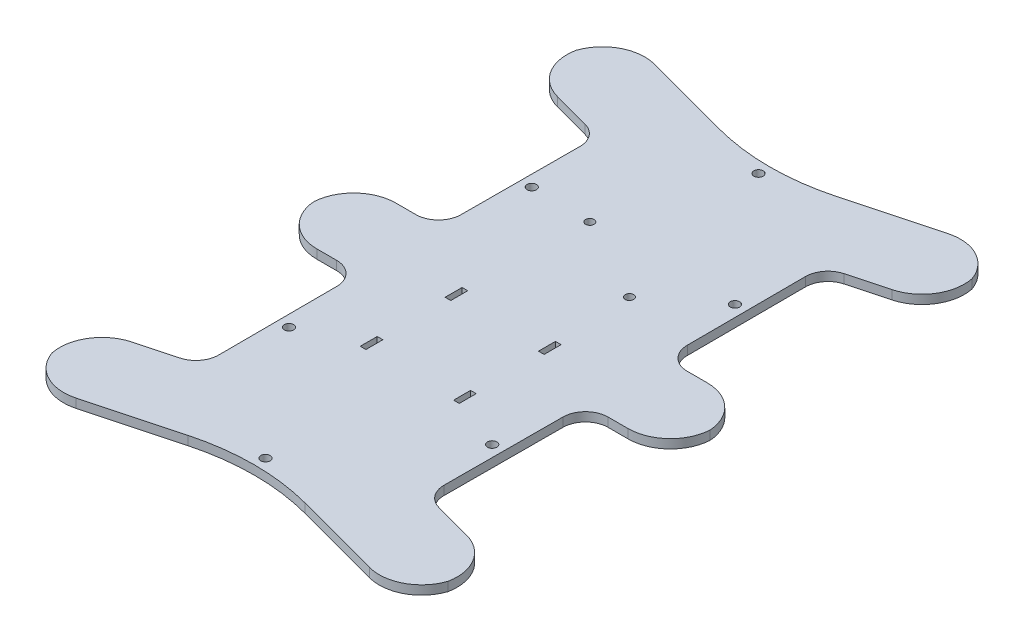
SolidWorks part; units mm, degrees
ref_plane "Front Plane" through (0, 0, 0) normal (0, 0, 1) x (1, 0, 0)
ref_plane "Top Plane" through (0, 0, 0) normal (0, 1, 0) x (1, 0, 0)
ref_plane "Right Plane" through (0, 0, 0) normal (1, 0, 0) x (0, 0, -1)
sketch "Sketch1" plane through (0, 0, 0) normal (0, 1, 0) x (1, 0, 0)
  line L0 (0, 32.1883) -> (0, -21.4181) construction
  line L1 (0, 0) -> (27.1703, 0) construction
  line L2 (-70, 14) -> (-40, 14)
  line L3 (-40, 14) -> (-39.8161, 70)
  line L4 (-39.8161, 70) -> (-73.6235, 79.0587)
  line L5 (-66.3765, 106.1046) -> (0, 88.3191)
  line L10 (-66.3765, 106.1046) -> (-73.6235, 79.0587) construction
  line L12 (-70, 14) -> (-70, -14) construction
  line L14 (-66.3765, -106.1046) -> (0, -88.3191)
  line L15 (-39.8161, -70) -> (-73.6235, -79.0587)
  line L16 (-40, -14) -> (-39.8161, -70)
  line L17 (-70, -14) -> (-40, -14)
  line L18 (66.3765, -106.1046) -> (0, -88.3191)
  line L19 (66.3765, 106.1046) -> (0, 88.3191)
  line L20 (70, 14) -> (70, -14) construction
  line L21 (66.3765, 106.1046) -> (73.6235, 79.0587) construction
  line L22 (70, -14) -> (40, -14)
  line L23 (40, -14) -> (39.8161, -70)
  line L24 (39.8161, -70) -> (73.6235, -79.0587)
  line L25 (39.8161, 70) -> (73.6235, 79.0587)
  line L26 (40, 14) -> (39.8161, 70)
  line L27 (70, 14) -> (40, 14)
  arc A0 (-70, 14) -> (-70, -14) centre (-70, 0) ccw
  arc A1 (-66.3765, 106.1046) -> (-73.6235, 79.0587) centre (-70, 92.5816) ccw
  arc A11 (-66.3765, -106.1046) -> (-73.6235, -79.0587) centre (-70, -92.5816) cw
  arc A18 (66.3765, -106.1046) -> (73.6235, -79.0587) centre (70, -92.5816) ccw
  arc A22 (66.3765, 106.1046) -> (73.6235, 79.0587) centre (70, 92.5816) cw
  arc A23 (70, 14) -> (70, -14) centre (70, 0) cw
  point P118 (-83.523, 96.2051)
  dimension "D2" = 14
  dimension "D3" = 70
  dimension "D1" = 75
  dimension "D5" = 30
  dimension "D6" = 35
  dimension "D7" = 56
extrude "Boss-Extrude1" add sketch "Sketch1" along normal blind 3.175
fillet "Fillet1" radius 80 2 edges at (0, 1.5875, -88.3191) (0, 1.5875, 88.3191)
fillet "Fillet2" radius 8 8 edges at (39.8161, 1.5875, 70) (40, 1.5875, 14) (40, 1.5875, -14) (39.8161, 1.5875, -70) (-39.8161, 1.5875, -70) (-40, 1.5875, -14) (-40, 1.5875, 14) (-39.8161, 1.5875, 70)
sketch "Sketch2" plane through (0, 3.175, 0) normal (0, 1, 0) x (1, 0, 0)
  line L0 (0, 91.1411) -> (0, -91.1411) construction
  line L1 (-84, 0) -> (84, 0) construction
  line L2 (39.9738, 21.9737) -> (39.8363, 63.8405) construction
  line L3 (-39.8363, 63.8405) -> (-39.9738, 21.9737) construction
  line L4 (-39.9051, 42.9071) -> (39.9051, 42.9071) construction
  arc A0 (-20.7055, 93.8671) -> (20.7055, 93.8671) centre (0, 171.1411) ccw construction
  arc A1 (20.7055, -93.8671) -> (-20.7055, -93.8671) centre (0, -171.1411) ccw construction
  arc A2 (-70, 14) -> (-70, -14) centre (-70, 0) ccw construction
  arc A3 (70, -14) -> (70, 14) centre (70, 0) ccw construction
  circle A4 centre (0, 87.1411) radius 1.65
  circle A5 centre (-35.905, 42.9071) radius 1.65
  circle A6 centre (35.905, 42.9071) radius 1.65
  circle A7 centre (35.905, -42.9071) radius 1.65
  circle A8 centre (0, -87.1411) radius 1.65
  circle A9 centre (-35.905, -42.9071) radius 1.65
  point P18 (39.9051, 42.9071)
  point P21 (-39.9051, 42.9071)
  dimension "D4" = 3.3
  dimension "D1" = 4
  dimension "D2" = 4
  dimension "D3" = 4
extrude "Cut-Extrude1" cut sketch "Sketch2" against normal blind 10
sketch "Sketch3" plane through (0, 3.175, 0) normal (0, 1, 0) x (1, 0, 0)
  arc A0 (13.5, 26.5) -> (16.5, 26.5) centre (15, 26.5) ccw construction
  arc A1 (16.5, 26.5) -> (13.5, 26.5) centre (15, 26.5) ccw construction
  arc A2 (-16.5, 42.5) -> (-13.5, 42.5) centre (-15, 42.5) ccw construction
  arc A3 (-13.5, 42.5) -> (-16.5, 42.5) centre (-15, 42.5) ccw construction
  arc A4 (13.5, 26.5) -> (16.5, 26.5) centre (15, 26.5) ccw
  arc A5 (16.5, 26.5) -> (13.5, 26.5) centre (15, 26.5) ccw
  arc A6 (-16.5, 42.5) -> (-13.5, 42.5) centre (-15, 42.5) ccw
  arc A7 (-13.5, 42.5) -> (-16.5, 42.5) centre (-15, 42.5) ccw
extrude "Cut-Extrude2" cut sketch "Sketch3" against normal blind 10
sketch "Sketch4" plane through (0, 3.175, 0) normal (0, 1, 0) x (1, 0, 0)
  line L0 (0, -91.1411) -> (0, 91.1411) construction
  line L1 (-15.5, -30.1411) -> (-15.5, -36.1411)
  line L2 (17.5, -0.1411) -> (15.5, -0.1411)
  line L3 (17.5, -0.1411) -> (17.5, -6.1411)
  line L4 (17.5, -6.1411) -> (15.5, -6.1411)
  line L5 (15.5, -0.1411) -> (15.5, -6.1411)
  line L6 (17.5, -30.1411) -> (15.5, -30.1411)
  line L7 (17.5, -30.1411) -> (17.5, -36.1411)
  line L8 (17.5, -36.1411) -> (15.5, -36.1411)
  line L9 (15.5, -30.1411) -> (15.5, -36.1411)
  line L10 (-17.5, -36.1411) -> (-15.5, -36.1411)
  line L11 (-17.5, -30.1411) -> (-17.5, -36.1411)
  line L12 (-17.5, -30.1411) -> (-15.5, -30.1411)
  line L13 (-15.5, -0.1411) -> (-15.5, -6.1411)
  line L14 (-17.5, -6.1411) -> (-15.5, -6.1411)
  line L15 (-17.5, -0.1411) -> (-17.5, -6.1411)
  line L16 (-17.5, -0.1411) -> (-15.5, -0.1411)
  arc A0 (20.7055, -93.8671) -> (-20.7055, -93.8671) centre (0, -171.1411) ccw construction
  arc A1 (-20.7055, 93.8671) -> (20.7055, 93.8671) centre (0, 171.1411) ccw construction
  dimension "D1" = 2
  dimension "D2" = 6
  dimension "D3" = 24
  dimension "D4" = 55
  dimension "D5" = 15.5
extrude "Cut-Extrude3" cut sketch "Sketch4" against normal blind 10
sketch "Sketch5" plane through (0, 3.175, 0) normal (0, 1, 0) x (1, 0, 0)
  line L0 (0, 91.1411) -> (0, -91.1411) construction
  line L1 (-84, 0) -> (84, 0) construction
  line L2 (-73.6235, 79.0587) -> (-66.3765, 106.1046)
  line L3 (73.6235, 79.0587) -> (66.3765, 106.1046)
  line L4 (73.6235, -79.0587) -> (66.3765, -106.1046)
  line L5 (-73.6235, -79.0587) -> (-66.3765, -106.1046)
  line L6 (-70, 14) -> (-70, -14)
  line L7 (70, 14) -> (70, -14)
  arc A0 (-20.7055, 93.8671) -> (20.7055, 93.8671) centre (0, 171.1411) ccw construction
  arc A1 (20.7055, -93.8671) -> (-20.7055, -93.8671) centre (0, -171.1411) ccw construction
  arc A2 (-70, 14) -> (-70, -14) centre (-70, 0) ccw construction
  arc A3 (70, -14) -> (70, 14) centre (70, 0) ccw construction
  arc A4 (-66.3765, 106.1046) -> (-73.6235, 79.0587) centre (-70, 92.5816) ccw
  arc A5 (66.3765, 106.1046) -> (73.6235, 79.0587) centre (70, 92.5816) cw
  arc A6 (66.3765, -106.1046) -> (73.6235, -79.0587) centre (70, -92.5816) ccw
  arc A7 (-66.3765, -106.1046) -> (-73.6235, -79.0587) centre (-70, -92.5816) cw
  arc A8 (-70, 14) -> (-70, -14) centre (-70, 0) ccw
  arc A9 (70, 14) -> (70, -14) centre (70, 0) cw
extrude "Cut-Extrude4" cut sketch "Sketch5" against normal blind 10
fillet "Fillet3" radius 15 12 edges at (66.3765, 1.5875, -106.1046) (73.6235, 1.5875, -79.0587) (70, 1.5875, -14) (70, 1.5875, 14) (73.6235, 1.5875, 79.0587) (66.3765, 1.5875, 106.1046) (-66.3765, 1.5875, 106.1046) (-73.6235, 1.5875, 79.0587) (-70, 1.5875, 14) (-70, 1.5875, -14) (-73.6235, 1.5875, -79.0587) (-66.3765, 1.5875, -106.1046)
equation "\"D2@Sketch2\"=\"D1@Sketch2\""
equation "\"D3@Sketch2\"=\"D1@Sketch2\""
